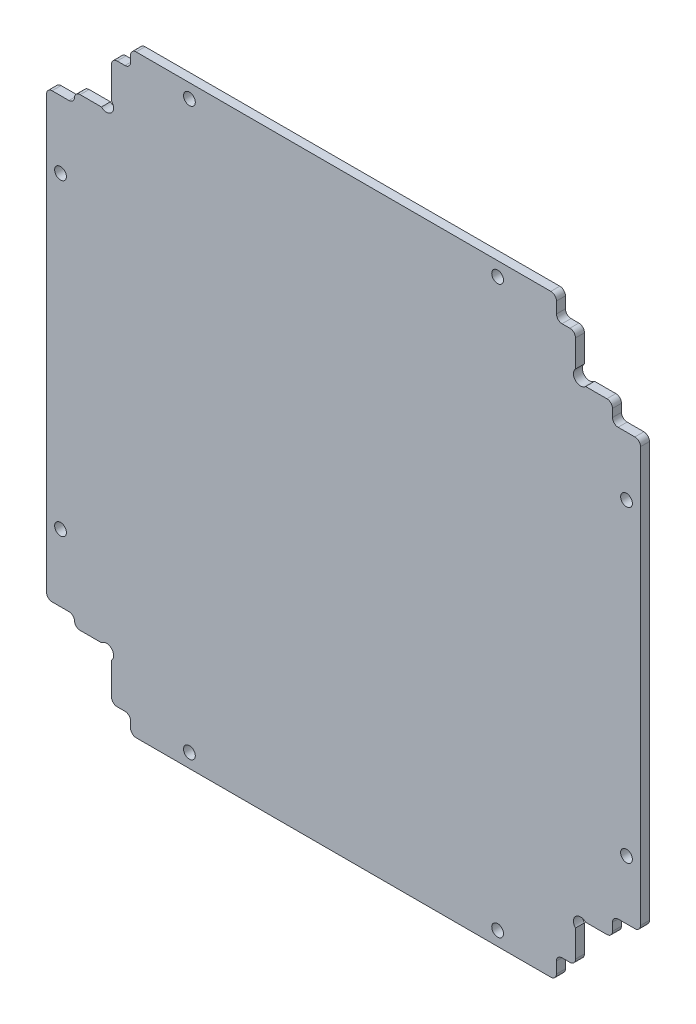
SolidWorks part; units mm, degrees
material "FR4_stuffedProtoboard"
ref_plane "Front Plane" through (0, 0, 0) normal (0, 0, 1) x (1, 0, 0)
ref_plane "Top Plane" through (0, 0, 0) normal (0, 1, 0) x (1, 0, 0)
ref_plane "Right Plane" through (0, 0, 0) normal (1, 0, 0) x (0, 0, -1)
sketch "Sketch1" plane through (0, 0, 0) normal (0, 0, 1) x (1, 0, 0)
  line L0 (53, 53) -> (-53, -53) construction
  line L1 (53, 53) -> (-53, 53)
  line L2 (53, 53) -> (53, -53)
  line L3 (53, -53) -> (-53, -53)
  line L4 (-53, 53) -> (-53, -53)
  point P4 (0, 0)
  dimension "D1" = 106
  dimension "D2" = 106
extrude "mainOutline" add sketch "Sketch1" along normal blind 1.6
sketch "axisLabels" plane through (0, 0, 0) normal (0, 0, -1) x (-1, 0, 0)
  text T0 "+Y"
  text T1 "+X"
sketch "Sketch4" plane through (0, 0, 0) normal (0, 0, -1) x (-1, 0, 0)
  line L1 (-41.4, -41.4) -> (-48, -41.4)
  line L3 (-41.4, -49) -> (-41.4, -41.4)
  line L5 (-60.1065, -39) -> (-49.9975, -39)
  line L7 (-39, -61.4521) -> (-39, -49.9)
  line L9 (39, -56.2753) -> (39, -49.9)
  line L10 (-53, 53) -> (53, 53) construction
  line L11 (41.4, -49.9) -> (41.4, -41.4)
  line L12 (-53, -53) -> (-53, 53) construction
  line L13 (41.4, -41.4) -> (48, -41.4)
  line L15 (48, -40.5) -> (55.5177, -40.5)
  line L17 (55.3838, 40.5) -> (48, 40.5)
  line L19 (39, 57.6877) -> (39, 49.9)
  line L21 (-39, 59.8804) -> (-39, 49.9)
  line L23 (-56.8428, 39) -> (-49.9975, 39)
  line L25 (-41.4, 41.4) -> (-41.4, 49)
  line L27 (-48, 41.4) -> (-41.4, 41.4)
  line L29 (41.4, 49.9) -> (41.4, 41.4)
  line L31 (48, 41.4) -> (41.4, 41.4)
  line L32 (-48, 41.4) -> (-48, 39)
  line L33 (-48, 39) -> (-49.9975, 39)
  line L34 (-41.4, 49) -> (-39, 49)
  line L35 (-39, 49) -> (-39, 49.9)
  line L36 (48, 40.5) -> (48, 41.4)
  line L37 (39, 49.9) -> (41.4, 49.9)
  line L38 (48, -40.5) -> (48, -41.4)
  line L39 (39, -49.9) -> (41.4, -49.9)
  line L40 (-41.4, -49) -> (-39, -49)
  line L41 (-39, -49) -> (-39, -49.9)
  line L42 (-49.9975, -39) -> (-48, -39)
  line L43 (-48, -39) -> (-48, -41.4)
  line L44 (-39, 59.8804) -> (-56.8428, 59.8804)
  line L45 (-56.8428, 59.8804) -> (-56.8428, 39)
  line L46 (53, 53) -> (53, -53) construction
  line L47 (-60.1065, -39) -> (-60.1065, -61.4521)
  line L48 (-60.1065, -61.4521) -> (-39, -61.4521)
  line L49 (39, -56.2753) -> (55.5177, -56.2753)
  line L50 (55.5177, -56.2753) -> (55.5177, -40.5)
  line L51 (55.3838, 40.5) -> (55.3838, 57.6877)
  line L52 (55.3838, 57.6877) -> (39, 57.6877)
  line L53 (53, -53) -> (-53, -53) construction
  dimension "D1" = 14
  dimension "D2" = 11.6
  dimension "D3" = 5
  dimension "D4" = 12.5
  dimension "D5" = 11.6
  dimension "D6" = 3.1
  dimension "D7" = 12.5
  dimension "D8" = 14
  dimension "D9" = 3.1
  dimension "D10" = 5
  dimension "D11" = 11.6
  dimension "D12" = 11.6
  dimension "D13" = 14
  dimension "D14" = 14
  dimension "D15" = 11.6
  dimension "D16" = 11.6
  dimension "D17" = 5
  dimension "D18" = 4
  dimension "D19" = 14
  dimension "D20" = 14
  dimension "D21" = 11.6
  dimension "D22" = 11.6
  dimension "D23" = 4
  dimension "D24" = 5
extrude "railCutouts" cut sketch "Sketch4" against normal through all
sketch "Sketch5" plane through (0, 0, 0) normal (0, 0, -1) x (-1, 0, 0)
  line L0 (-48.898, -39.898) -> (-52.4015, -43.4015) construction
  line L1 (-48, -40.7961) -> (-51.5035, -44.2995) construction
  line L2 (-49.7961, -39) -> (-53.2995, -42.5035) construction
  line L3 (-48, -41.4) -> (-48, -39) construction
  line L4 (-48, 39) -> (-48, 41.4) construction
  line L5 (-42.298, -42.298) -> (-45.4445, -45.4445) construction
  line L6 (-41.4, -43.1961) -> (-44.5465, -46.3425)
  line L7 (-43.1961, -41.4) -> (-46.3425, -44.5465)
  line L8 (-39.898, -49.898) -> (-42.6199, -52.6199) construction
  line L9 (-39, -50.7961) -> (-41.7219, -53.5179) construction
  line L10 (-40.7961, -49) -> (-43.5179, -51.7219) construction
  line L11 (39.898, -50.798) -> (41.4231, -52.3231) construction
  line L12 (40.7961, -49.9) -> (42.3212, -51.4251) construction
  line L13 (39, -51.6961) -> (40.5251, -53.2212) construction
  line L14 (42.298, -42.298) -> (44.0402, -44.0402) construction
  line L15 (43.1961, -41.4) -> (44.9382, -43.1422)
  line L16 (41.4, -43.1961) -> (43.1422, -44.9382)
  line L17 (48.898, -41.398) -> (49.9793, -42.4793) construction
  line L18 (49.7961, -40.5) -> (50.8774, -41.5813) construction
  line L19 (48, -42.2961) -> (49.0813, -43.3774) construction
  line L20 (48.898, 41.398) -> (50.5001, 43.0001) construction
  line L21 (48, 42.2961) -> (49.602, 43.8981) construction
  line L22 (49.7961, 40.5) -> (51.3981, 42.102) construction
  line L23 (42.298, 42.298) -> (44.029, 44.029) construction
  line L24 (41.4, 43.1961) -> (43.131, 44.927)
  line L25 (43.1961, 41.4) -> (44.927, 43.131)
  line L26 (39.898, 50.798) -> (41.2638, 52.1638) construction
  line L27 (39, 51.6961) -> (40.3658, 53.0618) construction
  line L28 (40.7961, 49.9) -> (42.1618, 51.2658) construction
  line L29 (-48.898, 39.898) -> (-50.0606, 41.0606) construction
  line L30 (-49.7961, 39) -> (-50.9587, 40.1626) construction
  line L31 (-48, 40.7961) -> (-49.1626, 41.9587) construction
  line L32 (-42.298, 42.298) -> (-43.7968, 43.7968) construction
  line L33 (-43.1961, 41.4) -> (-44.6948, 42.8988)
  line L34 (-41.4, 43.1961) -> (-42.8988, 44.6948)
  line L35 (-39.898, 49.898) -> (-41.256, 51.256) construction
  line L36 (-40.7961, 49) -> (-42.154, 50.358) construction
  line L37 (-39, 50.7961) -> (-40.358, 52.154) construction
  line L38 (-41.4, 41.4) -> (-41.4, 49) construction
  line L39 (-39, 49) -> (-39, 53) construction
  line L40 (39, 53) -> (39, 49.9) construction
  line L41 (41.4, 49.9) -> (41.4, 41.4) construction
  line L42 (48, 41.4) -> (48, 40.5) construction
  line L43 (39, -49.9) -> (39, -53) construction
  line L44 (41.4, -41.4) -> (41.4, -49.9) construction
  line L45 (53, -40.5) -> (48, -40.5) construction
  line L46 (-39, -53) -> (-39, -49) construction
  line L47 (-41.4, -49) -> (-41.4, -41.4) construction
  arc A0 (-48, -40.7961) -> (-49.7961, -39) centre (-48.898, -39.898) ccw construction
  arc A1 (-53.2995, -42.5035) -> (-51.5035, -44.2995) centre (-52.4015, -43.4015) ccw construction
  arc A2 (-41.4, -43.1961) -> (-43.1961, -41.4) centre (-42.298, -42.298) ccw
  arc A3 (-46.3425, -44.5465) -> (-44.5465, -46.3425) centre (-45.4445, -45.4445) ccw
  arc A4 (-39, -50.7961) -> (-40.7961, -49) centre (-39.898, -49.898) ccw construction
  arc A5 (-43.5179, -51.7219) -> (-41.7219, -53.5179) centre (-42.6199, -52.6199) ccw construction
  arc A6 (40.7961, -49.9) -> (39, -51.6961) centre (39.898, -50.798) ccw construction
  arc A7 (40.5251, -53.2212) -> (42.3212, -51.4251) centre (41.4231, -52.3231) ccw construction
  arc A8 (43.1961, -41.4) -> (41.4, -43.1961) centre (42.298, -42.298) ccw
  arc A9 (43.1422, -44.9382) -> (44.9382, -43.1422) centre (44.0402, -44.0402) ccw
  arc A10 (49.7961, -40.5) -> (48, -42.2961) centre (48.898, -41.398) ccw construction
  arc A11 (49.0813, -43.3774) -> (50.8774, -41.5813) centre (49.9793, -42.4793) ccw construction
  arc A12 (48, 42.2961) -> (49.7961, 40.5) centre (48.898, 41.398) ccw construction
  arc A13 (51.3981, 42.102) -> (49.602, 43.8981) centre (50.5001, 43.0001) ccw construction
  arc A14 (41.4, 43.1961) -> (43.1961, 41.4) centre (42.298, 42.298) ccw
  arc A15 (44.927, 43.131) -> (43.131, 44.927) centre (44.029, 44.029) ccw
  arc A16 (39, 51.6961) -> (40.7961, 49.9) centre (39.898, 50.798) ccw construction
  arc A17 (42.1618, 51.2658) -> (40.3658, 53.0618) centre (41.2638, 52.1638) ccw construction
  arc A18 (-49.7961, 39) -> (-48, 40.7961) centre (-48.898, 39.898) ccw construction
  arc A19 (-49.1626, 41.9587) -> (-50.9587, 40.1626) centre (-50.0606, 41.0606) ccw construction
  arc A20 (-43.1961, 41.4) -> (-41.4, 43.1961) centre (-42.298, 42.298) ccw
  arc A21 (-42.8988, 44.6948) -> (-44.6948, 42.8988) centre (-43.7968, 43.7968) ccw
  arc A22 (-40.7961, 49) -> (-39, 50.7961) centre (-39.898, 49.898) ccw construction
  arc A23 (-40.358, 52.154) -> (-42.154, 50.358) centre (-41.256, 51.256) ccw construction
  point P2 (-50.6498, -41.6498)
  point P9 (-43.8713, -43.8713)
  point P17 (-41.259, -51.259)
  point P24 (40.6606, -51.5606)
  point P31 (43.1691, -43.1691)
  point P38 (49.4387, -41.9387)
  point P45 (49.699, 42.199)
  point P52 (43.1635, 43.1635)
  point P59 (40.5809, 51.4809)
  point P66 (-49.4793, 40.4793)
  point P73 (-43.0474, 43.0474)
  point P80 (-40.577, 50.577)
  dimension "D14" = 1.27
  dimension "D1" = 45
  dimension "D3" = 45
  dimension "D4" = 45
  dimension "D5" = 45
  dimension "D6" = 45
  dimension "D7" = 45
  dimension "D8" = 45
  dimension "D9" = 45
  dimension "D10" = 45
  dimension "D11" = 45
  dimension "D12" = 45
  dimension "D13" = 45
extrude "dogbones" cut sketch "Sketch5" against normal through all
sketch "Sketch6" plane through (0, 0, 0) normal (0, 0, -1) x (-1, 0, 0)
  line L0 (-39, 50) -> (-39, 53) construction
  line L1 (-39, 49) -> (-39, 53) construction
  line L2 (-39, 53) -> (39, 53) construction
  line L3 (-40, 50) -> (-40, 53)
  line L4 (-38, 50) -> (-38, 53)
  line L5 (-49, 39) -> (-53, 39) construction
  line L6 (-53, 39) -> (-48, 39) construction
  line L7 (-49, 38) -> (-53, 38)
  line L8 (-49, 40) -> (-53, 40)
  line L9 (-49, -39) -> (-55.2142, -39) construction
  line L10 (-48, -39) -> (-53, -39) construction
  line L11 (-49, -40) -> (-55.2142, -40)
  line L12 (-49, -38) -> (-55.2142, -38)
  line L13 (-39, -50) -> (-39, -53.9161) construction
  line L14 (-39, -53) -> (-39, -49) construction
  line L15 (-38, -50) -> (-38, -53.9161)
  line L16 (-40, -50) -> (-40, -53.9161)
  line L17 (39, -50.9) -> (39, -54.538) construction
  line L18 (39, -49.9) -> (39, -53) construction
  line L19 (40, -50.9) -> (40, -54.538)
  line L20 (38, -50.9) -> (38, -54.538)
  line L21 (49, -40.5) -> (54.2026, -40.5) construction
  line L22 (53, -40.5) -> (48, -40.5) construction
  line L23 (49, -39.5) -> (54.2026, -39.5)
  line L24 (49, -41.5) -> (54.2026, -41.5)
  line L25 (49, 40.5) -> (54.5566, 40.5) construction
  line L26 (48, 40.5) -> (53, 40.5) construction
  line L27 (49, 41.5) -> (54.5566, 41.5)
  line L28 (49, 39.5) -> (54.5566, 39.5)
  line L29 (39, 50.9) -> (39, 55.8281) construction
  line L30 (39, 53) -> (39, 49.9) construction
  line L31 (38, 50.9) -> (38, 55.8281)
  line L32 (40, 50.9) -> (40, 55.8281)
  line L33 (-48, -41.4) -> (-48, -39) construction
  line L34 (-39, -49) -> (-41.4, -49) construction
  line L35 (41.4, -49.9) -> (39, -49.9) construction
  line L36 (48, -40.5) -> (48, -41.4) construction
  line L37 (48, 41.4) -> (48, 40.5) construction
  line L38 (39, 49.9) -> (41.4, 49.9) construction
  arc A0 (-40, 50) -> (-38, 50) centre (-39, 50) ccw
  arc A1 (-38, 53) -> (-40, 53) centre (-39, 53) ccw
  arc A2 (-49, 38) -> (-49, 40) centre (-49, 39) ccw
  arc A3 (-53, 40) -> (-53, 38) centre (-53, 39) ccw
  arc A4 (-49, -40) -> (-49, -38) centre (-49, -39) ccw
  arc A5 (-55.2142, -38) -> (-55.2142, -40) centre (-55.2142, -39) ccw
  arc A6 (-38, -50) -> (-40, -50) centre (-39, -50) ccw
  arc A7 (-40, -53.9161) -> (-38, -53.9161) centre (-39, -53.9161) ccw
  arc A8 (40, -50.9) -> (38, -50.9) centre (39, -50.9) ccw
  arc A9 (38, -54.538) -> (40, -54.538) centre (39, -54.538) ccw
  arc A10 (49, -39.5) -> (49, -41.5) centre (49, -40.5) ccw
  arc A11 (54.2026, -41.5) -> (54.2026, -39.5) centre (54.2026, -40.5) ccw
  arc A12 (49, 41.5) -> (49, 39.5) centre (49, 40.5) ccw
  arc A13 (54.5566, 39.5) -> (54.5566, 41.5) centre (54.5566, 40.5) ccw
  arc A14 (38, 50.9) -> (40, 50.9) centre (39, 50.9) ccw
  arc A15 (40, 55.8281) -> (38, 55.8281) centre (39, 55.8281) ccw
  point P6 (-39, 51.5)
  point P11 (-51, 39)
  point P21 (-52.1071, -39)
  point P30 (-39, -51.958)
  point P39 (39, -52.719)
  point P48 (51.6013, -40.5)
  point P57 (51.7783, 40.5)
  point P66 (39, 53.364)
  point P75 (-39, 49)
  dimension "D1" = 1
extrude "solarFillets" cut sketch "Sketch6" against normal through all
fillet "handlingFillets" radius 1 16 edges at (-41.4, -49.9, 0.8) (-38, -53, 0.8) (-53, -39.5, 0.8) (-48, -41.4, 0.8) (-48, 41.4, 0.8) (-53, 39.5, 0.8) (-41.4, 49.9, 0.8) (-38, 53, 0.8) (38, 53, 0.8) (41.4, 49, 0.8) (48, 41.4, 0.8) (53, 38, 0.8) (53, -38, 0.8) (48, -41.4, 0.8) (41.4, -49, 0.8) (38, -53, 0.8)
sketch "Sketch7" plane through (0, 0, 1.6) normal (0, 0, 1) x (1, 0, 0)
  line L0 (-37, -53) -> (37, -53) construction
  line L1 (-53, 38.5) -> (-53, -38.5) construction
  line L2 (37, 53) -> (-37, 53) construction
  line L3 (-31.37, 28.67) -> (-31.37, 31.21) construction
  line L4 (-31.37, 31.21) -> (-28.83, 31.21) construction
  line L5 (-28.83, 31.21) -> (-28.83, 28.67) construction
  line L6 (-28.83, 28.67) -> (-31.37, 28.67) construction
  line L7 (-31.37, 28.67) -> (-28.83, 31.21) construction
  circle A1 centre (-28.4723, -17.925) radius 0.8
  circle A3 centre (-28.4723, -33.775) radius 0.8
  circle A5 centre (-31.37, 28.67) radius 0.425
  circle A7 centre (-28.83, 28.67) radius 0.425
  circle A9 centre (-30.1, 29.94) radius 0.425
  circle A10 centre (-28.83, 31.21) radius 0.425
  circle A11 centre (-31.37, 31.21) radius 0.425
  circle A12 centre (-31.37, 21.27) radius 0.425
  circle A13 centre (-28.83, 21.27) radius 0.425
  circle A14 centre (-30.1, 22.54) radius 0.425
  circle A15 centre (-28.83, 23.81) radius 0.425
  circle A16 centre (-31.37, 23.81) radius 0.425
  circle A17 centre (-31.37, 13.87) radius 0.425
  circle A18 centre (-28.83, 13.87) radius 0.425
  circle A19 centre (-30.1, 15.14) radius 0.425
  circle A20 centre (-28.83, 16.41) radius 0.425
  circle A21 centre (-31.37, 16.41) radius 0.425
  point P13 (-30.1, 29.94)
  dimension "D8" = 1.6
  dimension "D9" = 3
  dimension "D6" = 0.85
  dimension "D1" = 19.225
  dimension "D2" = 24.5277
  dimension "D3" = 15.85
  dimension "D4" = 23.06
  dimension "D5" = 22.9
  dimension "D7" = 2.54
  dimension "D10" = 7.4
extrude "connectorHoles" [suppressed] cut sketch "Sketch7" against normal through all
hole_wizard "M2 Clearance Hole1" positions "Sketch8" profile "Sketch9" hole size "M2" standard "ANSI Metric" end condition through all
sketch "Sketch8" plane through (0, 0, 0) normal (0, 0, -1) x (-1, 0, 0)
  line L0 (53, 38.5) -> (53, -38.5) construction
  line L1 (37, -53) -> (-37, -53) construction
  line L2 (-53, -37) -> (-53, 37) construction
  line L3 (53, 0) -> (-53, 0) construction
  line L5 (0, -53) -> (0, -11.6379) construction
  point P0 (50.5, -27.5)
  point P1 (27.5, -50.5)
  point P5 (-50.5, -27.5)
  point P30 (-27.5, -50.5)
  point P31 (-27.5, 50.5)
  point P32 (-50.5, 27.5)
  point P33 (27.5, 50.5)
  point P34 (50.5, 27.5)
  dimension "D1" = 2.5
  dimension "D2" = 2.5
  dimension "D3" = 55
  dimension "D4" = 2.5
  dimension "D5" = 55
  dimension "D6" = 55
sketch "Sketch9" plane through (-50.5, -27.5, 0) normal (1, 0, 0) x (0, 1, 0)
  line L0 (0, 0) -> (0, 1.6)
  line L1 (0, 1.6) -> (1.05, 1.6)
  line L2 (1.05, 1.6) -> (1.05, 0)
  line L5 (1.05, 0) -> (0, 0)
  line L11 (0, -6.35) -> (0, 107.95) construction
  dimension "Thru Hole Dia." = 2.1
  dimension "Thru Hole Depth" = 1.6
